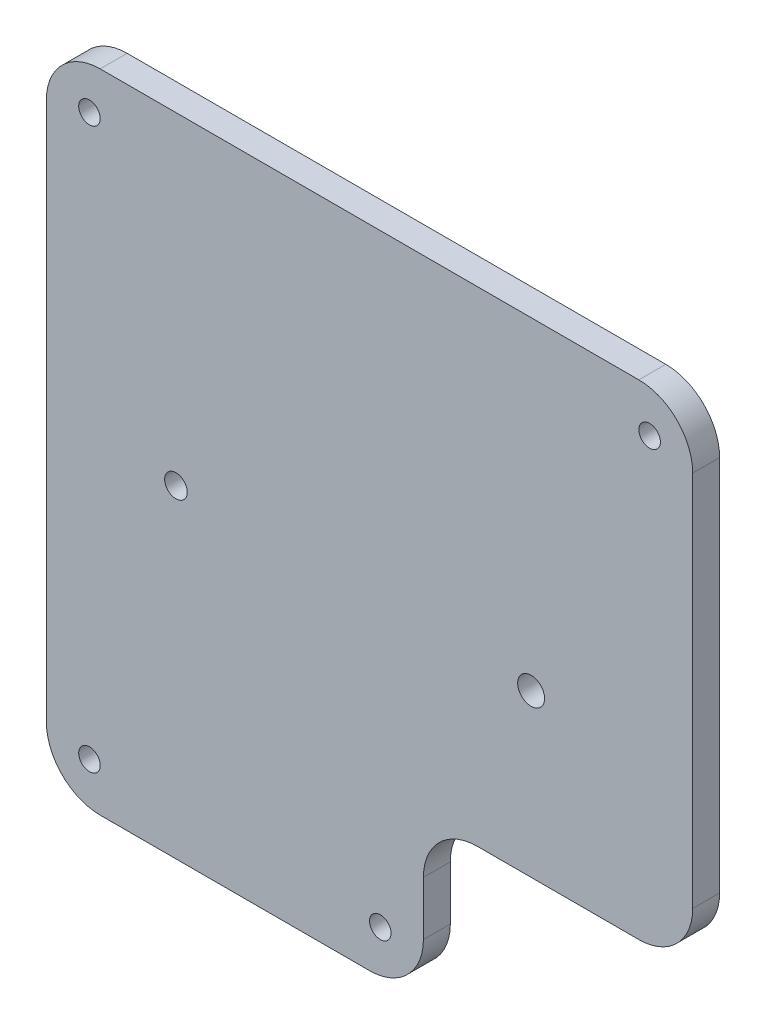
SolidWorks part; units mm, degrees
ref_plane "Alzado" through (0, 0, 0) normal (0, 0, 1) x (1, 0, 0)
ref_plane "Planta" through (0, 0, 0) normal (0, 1, 0) x (1, 0, 0)
ref_plane "Vista lateral" through (0, 0, 0) normal (1, 0, 0) x (0, 0, -1)
sketch "Croquis1" plane through (0, 0, 0) normal (0, 0, 1) x (1, 0, 0)
  line L0 (110, 30) -> (80, 30)
  line L1 (10, 0) -> (60, 0)
  line L2 (0, 10) -> (0, 110)
  line L3 (10, 120) -> (110, 120)
  line L4 (120, 40) -> (120, 110)
  line L5 (70, 20) -> (70, 10)
  arc A0 (10, 0) -> (0, 10) centre (10, 10) cw
  arc A1 (70, 10) -> (60, 0) centre (60, 10) cw
  arc A2 (110, 120) -> (120, 110) centre (110, 110) cw
  arc A3 (0, 110) -> (10, 120) centre (10, 110) cw
  arc A4 (80, 30) -> (70, 20) centre (80, 20) ccw
  arc A5 (110, 30) -> (120, 40) centre (110, 40) ccw
  point P7 (0, 0)
  point P10 (120, 0)
  point P15 (0, 120)
  dimension "D3" = 10
  dimension "D6" = 10
  dimension "D1" = 120
  dimension "D2" = 120
  dimension "D4" = 30
  dimension "D5" = 50
extrude "Saliente-Extruir1" add sketch "Croquis1" along normal blind 5
sketch "Croquis2" plane through (0, 0, 5) normal (0, 0, 1) x (1, 0, 0)
  line L0 (60, 120) -> (60, 75.4201) construction
  line L1 (110, 120) -> (10, 120) construction
  line L2 (0, 110) -> (0, 10) construction
  line L3 (0, 60) -> (90, 60) construction
  line L4 (120, 40) -> (120, 110) construction
  line L5 (70, 10) -> (70, 20) construction
  line L6 (10, 0) -> (60, 0) construction
  circle A0 centre (8, 112) radius 2
  circle A1 centre (8, 8) radius 2
  circle A2 centre (112, 8) radius 2
  circle A3 centre (112, 112) radius 2
  circle A4 centre (90, 60) radius 2.5
  circle A5 centre (62, 8) radius 2
  circle A6 centre (24.06, 60) radius 2.1
  point P23 (70, 15)
  dimension "D3" = 4
  dimension "D4" = 5
  dimension "D6" = 4
  dimension "D9" = 4.2
  dimension "D1" = 8
  dimension "D2" = 8
  dimension "D5" = 30
  dimension "D7" = 8
  dimension "D8" = 8
  dimension "D10" = 65.94
extrude "Cortar-Extruir1" cut sketch "Croquis2" against normal blind 10
sketch "Croquis3" plane through (0, 0, 5) normal (0, 0, 1) x (1, 0, 0)
  line L6 (70, 10) -> (70, 20)
  line L7 (80, 30) -> (110, 30)
  line L8 (120, 40) -> (120, 110)
  line L9 (110, 120) -> (10, 120)
  line L10 (0, 110) -> (0, 10)
  line L11 (10, 0) -> (60, 0)
  line L12 (70, 10) -> (70, 20)
  line L13 (80, 30) -> (110, 30)
  line L14 (120, 40) -> (120, 110)
  line L15 (110, 120) -> (10, 120)
  line L16 (0, 110) -> (0, 10)
  line L17 (10, 0) -> (60, 0)
  circle A0 centre (112, 112) radius 2 construction
  circle A1 centre (90, 60) radius 2.5 construction
  circle A2 centre (62, 8) radius 2 construction
  circle A3 centre (8, 8) radius 2 construction
  circle A4 centre (24.06, 60) radius 2.1 construction
  circle A5 centre (8, 112) radius 2 construction
  arc A6 (60, 0) -> (70, 10) centre (60, 10) ccw
  arc A7 (80, 30) -> (70, 20) centre (80, 20) ccw
  arc A8 (110, 30) -> (120, 40) centre (110, 40) ccw
  arc A9 (120, 110) -> (110, 120) centre (110, 110) ccw
  arc A10 (10, 120) -> (0, 110) centre (10, 110) ccw
  arc A11 (0, 10) -> (10, 0) centre (10, 10) ccw
  arc A12 (60, 0) -> (70, 10) centre (60, 10) ccw
  arc A13 (80, 30) -> (70, 20) centre (80, 20) ccw
  arc A14 (110, 30) -> (120, 40) centre (110, 40) ccw
  arc A15 (120, 110) -> (110, 120) centre (110, 110) ccw
  arc A16 (10, 120) -> (0, 110) centre (10, 110) ccw
  arc A17 (0, 10) -> (10, 0) centre (10, 10) ccw
  circle A18 centre (112, 112) radius 2
  circle A19 centre (90, 60) radius 2.5
  circle A20 centre (62, 8) radius 2
  circle A21 centre (8, 8) radius 2
  circle A22 centre (24.06, 60) radius 2.1
  circle A23 centre (8, 112) radius 2
  dimension "D1" = 0
